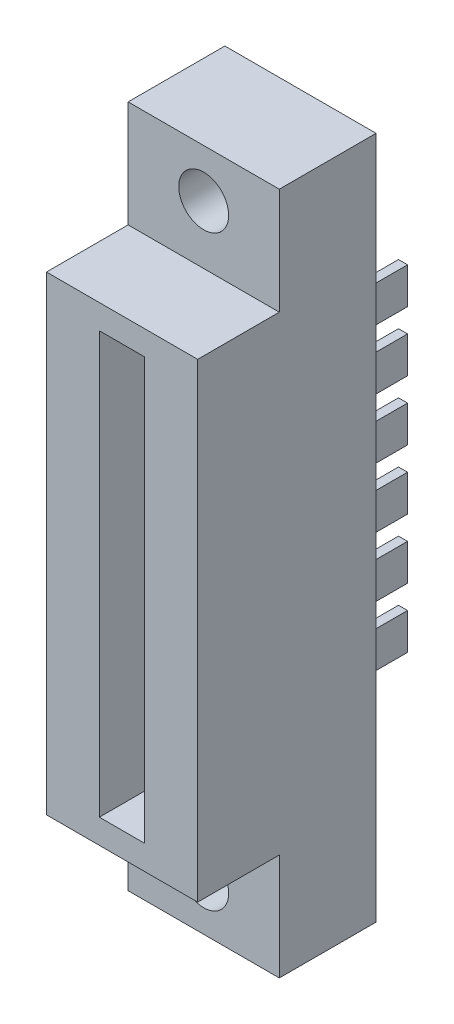
SolidWorks part; units mm, degrees
ref_plane "前视基准面" through (0, 0, 0) normal (0, 0, 1) x (1, 0, 0)
ref_plane "上视基准面" through (0, 0, 0) normal (0, 1, 0) x (1, 0, 0)
ref_plane "右视基准面" through (0, 0, 0) normal (1, 0, 0) x (0, 0, -1)
sketch "草图1" plane through (0, 0, 0) normal (0, 0, 1) x (1, 0, 0)
  line L0 (-109.3839, 0) -> (104.0581, 0) construction
  line L1 (0, 55.921) -> (0, -57.9694) construction
  line L3 (-5, 22.59) -> (5, 22.59)
  line L4 (-5, 22.59) -> (-5, -22.59)
  line L5 (-5, -22.59) -> (5, -22.59)
  line L6 (5, 22.59) -> (5, -22.59)
  dimension "D1" = 45.18
  dimension "D2" = 10
extrude "拉伸1" add sketch "草图1" along normal blind 6.4
sketch "草图2" plane through (0, 0, 6.4) normal (0, 0, 1) x (1, 0, 0)
  line L0 (-8.8552, 0) -> (12.3972, 0) construction
  line L1 (0, 34.0186) -> (0, -32.3951) construction
  line L3 (-5, 22.59) -> (-5, -22.59) construction
  line L4 (-5, 15.545) -> (5, 15.545)
  line L5 (-5, 15.545) -> (-5, -15.545)
  line L6 (-5, -15.545) -> (5, -15.545)
  line L7 (5, 15.545) -> (5, -15.545)
  line L8 (5, -22.59) -> (5, 22.59) construction
  dimension "D1" = 31.09
extrude "拉伸2" add sketch "草图2" along normal blind 5.4
sketch "草图3" plane through (0, 0, 6.4) normal (0, 0, 1) x (1, 0, 0)
  line L0 (-13.2827, 0) -> (15.9393, 0) construction
  line L1 (0, 37.0608) -> (0, -37.8999) construction
  circle A0 centre (0, 19.415) radius 1.65
  circle A1 centre (0, -19.415) radius 1.65
  dimension "D1" = 3.3
  dimension "D2" = 38.83
extrude "切除-拉伸1" cut sketch "草图3" against normal blind 15.3
sketch "草图4" plane through (0, 0, 0) normal (0, 0, -1) x (-1, 0, 0)
  line L0 (-14.0207, 0) -> (16.6772, 0) construction
  line L1 (0, 36.8227) -> (0, -37.1179) construction
  line L2 (-5.8349, 1.98) -> (7.2578, 1.98) construction
  line L3 (-2.0811, 3.18) -> (-1.4811, 3.18)
  line L4 (-2.0811, 3.18) -> (-2.0811, 0.78)
  line L5 (-2.0811, 0.78) -> (-1.4811, 0.78)
  line L6 (-1.4811, 3.18) -> (-1.4811, 0.78)
  line L7 (-1.7811, 6.5923) -> (-1.7811, -1.6245) construction
  line L8 (1.7811, 6.5923) -> (1.7811, -1.6245) construction
  line L9 (1.4811, 3.18) -> (1.4811, 0.78)
  line L10 (2.0811, 0.78) -> (1.4811, 0.78)
  line L11 (2.0811, 3.18) -> (2.0811, 0.78)
  line L12 (2.0811, 3.18) -> (1.4811, 3.18)
  line L13 (-2.0811, 7.14) -> (-1.4811, 7.14)
  line L14 (-2.0811, 7.14) -> (-2.0811, 4.74)
  line L15 (-2.0811, 4.74) -> (-1.4811, 4.74)
  line L16 (-1.4811, 7.14) -> (-1.4811, 4.74)
  line L17 (1.4811, 7.14) -> (1.4811, 4.74)
  line L18 (2.0811, 4.74) -> (1.4811, 4.74)
  line L19 (2.0811, 7.14) -> (2.0811, 4.74)
  line L20 (2.0811, 7.14) -> (1.4811, 7.14)
  line L21 (-2.0811, 11.1) -> (-1.4811, 11.1)
  line L22 (-2.0811, 11.1) -> (-2.0811, 8.7)
  line L23 (-2.0811, 8.7) -> (-1.4811, 8.7)
  line L24 (-1.4811, 11.1) -> (-1.4811, 8.7)
  line L25 (1.4811, 11.1) -> (1.4811, 8.7)
  line L26 (2.0811, 8.7) -> (1.4811, 8.7)
  line L27 (2.0811, 11.1) -> (2.0811, 8.7)
  line L28 (2.0811, 11.1) -> (1.4811, 11.1)
  line L45 (2.0811, -11.1) -> (1.4811, -11.1)
  line L46 (2.0811, -11.1) -> (2.0811, -8.7)
  line L47 (2.0811, -8.7) -> (1.4811, -8.7)
  line L48 (1.4811, -11.1) -> (1.4811, -8.7)
  line L49 (-1.4811, -11.1) -> (-1.4811, -8.7)
  line L50 (-2.0811, -8.7) -> (-1.4811, -8.7)
  line L51 (-2.0811, -11.1) -> (-2.0811, -8.7)
  line L52 (-2.0811, -11.1) -> (-1.4811, -11.1)
  line L53 (2.0811, -7.14) -> (1.4811, -7.14)
  line L54 (2.0811, -7.14) -> (2.0811, -4.74)
  line L55 (2.0811, -4.74) -> (1.4811, -4.74)
  line L56 (1.4811, -7.14) -> (1.4811, -4.74)
  line L57 (-1.4811, -7.14) -> (-1.4811, -4.74)
  line L58 (-2.0811, -4.74) -> (-1.4811, -4.74)
  line L59 (-2.0811, -7.14) -> (-2.0811, -4.74)
  line L60 (-2.0811, -7.14) -> (-1.4811, -7.14)
  line L61 (2.0811, -3.18) -> (1.4811, -3.18)
  line L62 (2.0811, -3.18) -> (2.0811, -0.78)
  line L63 (2.0811, -0.78) -> (1.4811, -0.78)
  line L64 (1.4811, -3.18) -> (1.4811, -0.78)
  line L65 (-1.4811, -3.18) -> (-1.4811, -0.78)
  line L66 (-2.0811, -0.78) -> (-1.4811, -0.78)
  line L67 (-2.0811, -3.18) -> (-2.0811, -0.78)
  line L68 (-2.0811, -3.18) -> (-1.4811, -3.18)
  line L69 (-2.0811, 15.06) -> (-1.4811, 15.06) [skipped]
  line L70 (-2.0811, 15.06) -> (-2.0811, 12.66) [skipped]
  line L71 (-2.0811, 12.66) -> (-1.4811, 12.66) [skipped]
  line L72 (-1.4811, 15.06) -> (-1.4811, 12.66) [skipped]
  line L73 (1.4811, 15.06) -> (1.4811, 12.66) [skipped]
  line L74 (2.0811, 12.66) -> (1.4811, 12.66) [skipped]
  line L75 (2.0811, 15.06) -> (2.0811, 12.66) [skipped]
  line L76 (2.0811, 15.06) -> (1.4811, 15.06) [skipped]
  dimension "D1" = 2.4
  dimension "D2" = 0.6
  dimension "D3" = 1.98
  dimension "D4" = 3.5623
  dimension "D5" = 4
extrude "拉伸3" add sketch "草图4" along normal blind 5
sketch "草图5" plane through (0, 0, 11.8) normal (0, 0, 1) x (1, 0, 0)
  line L0 (-15.4965, 0) -> (18.3007, 0) construction
  line L1 (0, 29.0007) -> (0, -15.545) construction
  line L2 (-5, -15.545) -> (5, -15.545) construction
  line L4 (-1.5, 13.93) -> (1.5, 13.93)
  line L5 (-1.5, 13.93) -> (-1.5, -13.93)
  line L6 (-1.5, -13.93) -> (1.5, -13.93)
  line L7 (1.5, 13.93) -> (1.5, -13.93)
  dimension "D1" = 3
  dimension "D2" = 27.86
extrude "切除-拉伸2" cut sketch "草图5" against normal blind 8
